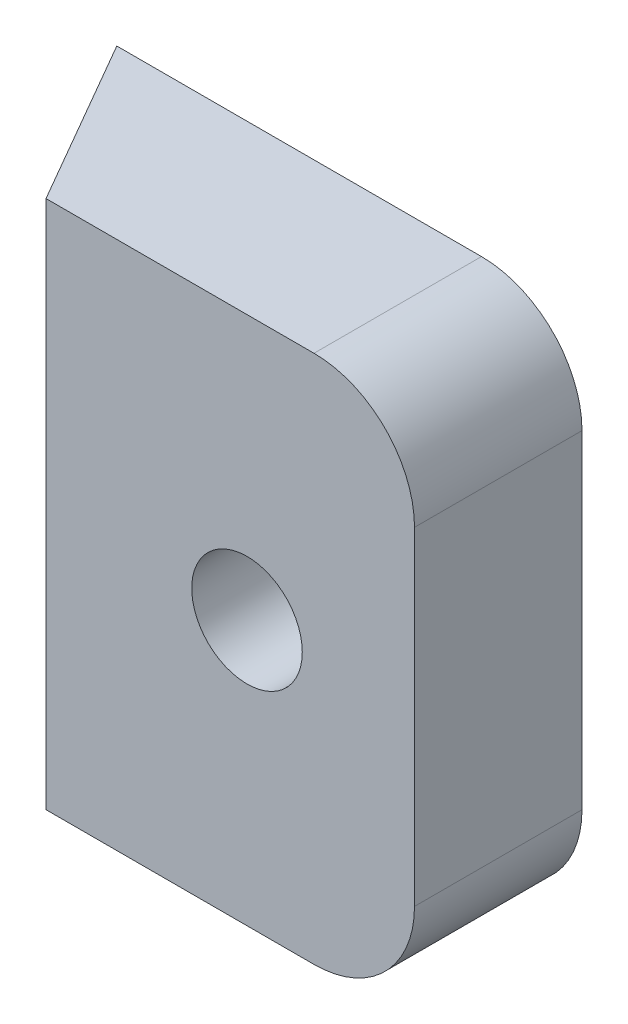
SolidWorks part; units mm, degrees
material "Сплав 2024"
ref_plane "Спереди" through (0, 0, 0) normal (0, 0, 1) x (1, 0, 0)
ref_plane "Сверху" through (0, 0, 0) normal (0, 1, 0) x (1, 0, 0)
ref_plane "Справа" through (0, 0, 0) normal (1, 0, 0) x (0, 0, -1)
sketch "Эскиз1" plane through (0, 0, 0) normal (0, 1, 0) x (1, 0, 0)
  line L0 (0, 0) -> (0, 5)
  line L1 (0, 5) -> (-13.8868, 5)
  line L2 (-13.8868, 5) -> (-11, 0)
  line L3 (-11, 0) -> (0, 0)
  dimension "D1" = 11
  dimension "D2" = 60
  dimension "D3" = 5
extrude "Бобышка-Вытянуть1" add sketch "Эскиз1" along normal blind 15.8
fillet "Скругление1" radius 3 2 edges at (0, 0, -2.5) (0, 15.8, -2.5)
sketch "Эскиз2" plane through (0, 0, 0) normal (0, 0, 1) x (1, 0, 0)
  line L0 (0, 7.9) -> (-7.9383, 7.9) construction
  line L1 (0, 12.8) -> (0, 3) construction
  point P4 (-5, 7.9)
  dimension "D1" = 5
hole_wizard "Отверстие обработанное метчиком M4x0.71" positions "Эскиз4" profile "Эскиз3" tap size "M4x0.7" standard "Ansi Metric" end condition through all
sketch "Эскиз4" plane through (0, 0, 0) normal (0, 0, 1) x (1, 0, 0)
  point P0 (-5, 7.9)
sketch "Эскиз3" plane through (-5, 7.9, 0) normal (1, 0, 0) x (0, -1, 0)
  line L0 (0, 0) -> (0, 5)
  line L1 (0, 5) -> (1.65, 5)
  line L2 (1.65, 5) -> (1.65, 0)
  line L5 (1.65, 0) -> (0, 0)
  line L11 (0, -6.35) -> (0, 107.95) construction
  dimension "Диаметр резьбы" = 3.3
  dimension "Глубина проходного сверла" = 5
